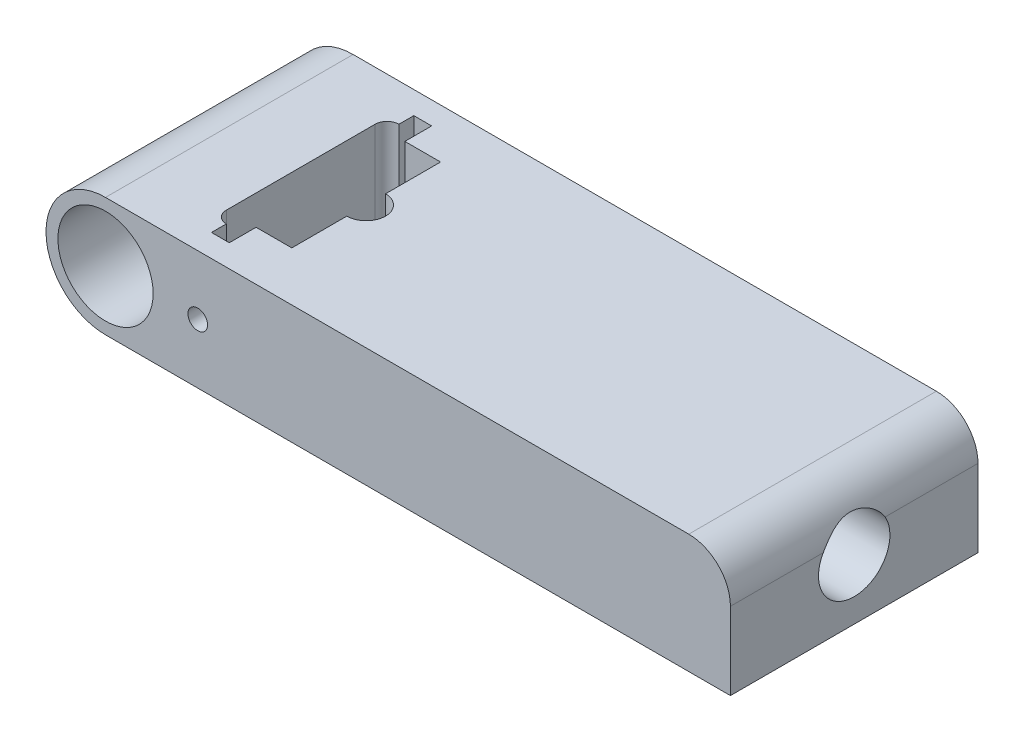
SolidWorks part; units mm, degrees
material "Alu 2017 (AU4G)"
ref_plane "Face" through (0, 0, 0) normal (0, 0, 1) x (1, 0, 0)
ref_plane "Dessus" through (0, 0, 0) normal (0, 1, 0) x (1, 0, 0)
ref_plane "Droite" through (0, 0, 0) normal (1, 0, 0) x (0, 0, -1)
sketch "Esquisse1" plane through (0, 0, 0) normal (0, 0, 1) x (1, 0, 0)
  line L0 (0, -10) -> (105, -10)
  line L2 (0, 10) -> (105, 10)
  line L3 (105, 10) -> (105, -10)
  arc A0 (0, 10) -> (0, -10) centre (0, 0) ccw
  circle A1 centre (0, 0) radius 8
  dimension "D3" = 16
  dimension "D1" = 20
  dimension "D2" = 105
extrude "Boss.-Extru.1" add sketch "Esquisse1" along normal mid plane 41.6
hole_wizard "Diamètre du perçage Ø12.0 (12)1" positions "Esquisse4" profile "Esquisse3" hole size "Ø12.0" standard "ISO"
sketch "Esquisse4" plane through (105, 0, 0) normal (1, 0, 0) x (0, 0, -1)
  point P0 (0, 0)
sketch "Esquisse3" plane through (105, 0, 0) normal (0, 1, 0) x (0, 0, -1)
  line L0 (0, 0) -> (0, 91.6052)
  line L1 (0, 91.6052) -> (6, 88)
  line L2 (6, 88) -> (6, 0)
  line L5 (6, 0) -> (0, 0)
  line L10 (0, 91.6052) -> (-6, 88) construction
  line L11 (0, -6.35) -> (0, 107.95) construction
  dimension "Diamètre du perçage" = 12
  dimension "Profondeur du perçage" = 88
  dimension "Angle de pointe" = 118
fillet "Congé1" radius 7 1 edges at (105, 10, 0)
sketch "Esquisse5" plane through (0, 10, 0) normal (0, 1, 0) x (1, 0, 0)
  line L0 (0, 0) -> (98, 0) construction
  line L1 (0, -20.8) -> (0, 20.8) construction
  line L2 (98, -20.8) -> (98, 20.8) construction
  line L3 (12, -12.5) -> (12, 12.5)
  line L4 (14, 14.5) -> (14, 17)
  line L5 (14, 17) -> (17, 17)
  line L6 (17, 17) -> (17, 12.5)
  line L7 (17, 12.5) -> (23, 12.5)
  line L8 (23, 12.5) -> (23, -12.5)
  line L9 (17, -12.5) -> (23, -12.5)
  line L10 (17, -17) -> (17, -12.5)
  line L11 (14, -17) -> (17, -17)
  line L12 (14, -14.5) -> (14, -17)
  line L13 (105, 20.8) -> (105, 5.1962) construction
  arc A0 (12, 12.5) -> (14, 14.5) centre (14, 12.5) cw
  arc A1 (12, -12.5) -> (14, -14.5) centre (14, -12.5) ccw
  point P19 (23, 0)
  point P22 (12, 0)
  dimension "D1" = 25
  dimension "D2" = 29
  dimension "D3" = 5
  dimension "D4" = 11
  dimension "D5" = 82
  dimension "D6" = 25
  dimension "D7" = 34
extrude "Enlèv. mat.-Extru.1" cut sketch "Esquisse5" against normal through all
sketch "Esquisse6" plane through (0, 10, 0) normal (0, 1, 0) x (1, 0, 0)
  line L0 (23, -12.5) -> (23, 12.5) construction
  circle A0 centre (23, 0) radius 3.25
  dimension "D1" = 6.5
extrude "Enlèv. mat.-Extru.2" cut sketch "Esquisse6" against normal blind 10
hole_wizard "Trou taraudé M41" positions "Esquisse8" profile "Esquisse7" tap size "M4" standard "ISO" end condition through all
sketch "Esquisse8" plane through (0, 0, -20.8) normal (0, 0, -1) x (-1, 0, 0)
  line L0 (-105, -10) -> (-105, 3) construction
  point P0 (-15.5, 0)
  dimension "D1" = 89.5
sketch "Esquisse7" plane through (15.5, 0, -20.8) normal (1, 0, 0) x (0, 1, 0)
  line L0 (0, 0) -> (0, 41.6)
  line L1 (0, 41.6) -> (1.65, 41.6)
  line L2 (1.65, 41.6) -> (1.65, 0)
  line L5 (1.65, 0) -> (0, 0)
  line L11 (0, -6.35) -> (0, 107.95) construction
  dimension "Diamètre du trou pour taraudage jusqu'au prochain" = 3.3
  dimension "Profondeur du trou pour taraudage jusqu'au prochain" = 41.6
cosmetic thread "Filetage de perçage1" parameters "D2"=4
